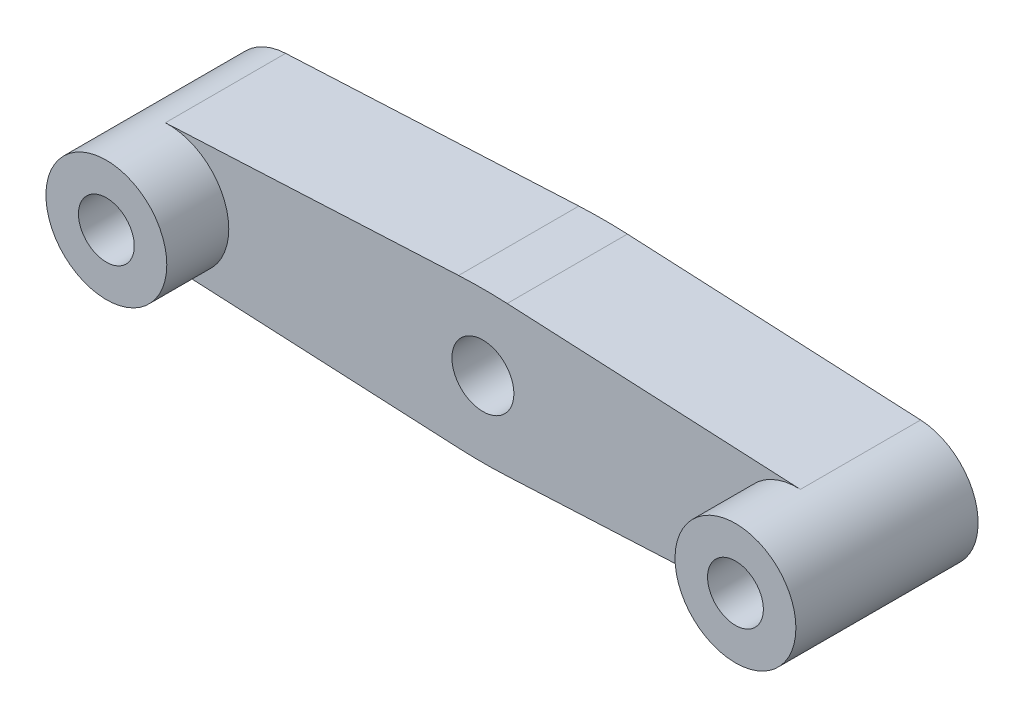
SolidWorks part; units mm, degrees
material "6061 합금"
ref_plane "정면" through (0, 0, 0) normal (0, 0, 1) x (1, 0, 0)
ref_plane "윗면" through (0, 0, 0) normal (0, 1, 0) x (1, 0, 0)
ref_plane "우측면" through (0, 0, 0) normal (1, 0, 0) x (0, 0, -1)
sketch "스케치1" plane through (0, 0, 0) normal (0, 0, 1) x (1, 0, 0)
  line L0 (0, -12.25) -> (0, 12.25) construction
  line L1 (-51.2275, 9.7383) -> (0, 12.25)
  line L2 (-51.2275, -9.7383) -> (0, -12.25)
  line L3 (51.2275, -9.7383) -> (0, -12.25)
  line L4 (51.2275, 9.7383) -> (0, 12.25)
  circle A0 centre (-50.75, 0) radius 9.75
  circle A1 centre (50.75, 0) radius 9.75
  dimension "D1" = 24.5
  dimension "D2" = 19.5
  dimension "D3" = 101.5
extrude "보스-돌출1" add sketch "스케치1" along normal blind 19.4 contours A0 | L2 L0 L1 A0 | L0 L3 A1 L4 | A1 region at (-20.9946, 0, 0) region at (20.9946, 0, 0) region at (-50.75, 0, 0) region at (50.75, 0, 0)
extrude "보스-돌출2" add sketch "스케치1<3>" along normal blind 29.4 contours A0 | A1 region at (-50.75, 0, 0) region at (50.75, 0, 0)
sketch "스케치1<3>" plane through (0, 0, 0) normal (0, 0, 1) x (1, 0, 0) same geometry as "스케치1"
sketch "스케치2" plane through (0, 0, 0) normal (0, 0, 1) x (1, 0, 0)
  circle A0 centre (0, 0) radius 5
  dimension "D1" = 10
extrude "컷-돌출1" cut sketch "스케치2" along normal through all
fillet "필렛1" radius 80 2 edges at (0, -12.25, 9.7) (0, 12.25, 9.7)
hole_wizard "M8 소켓 머리 캡 나사용 카운터보어1" positions "스케치3" profile "스케치4" counterbore size "M8" standard "Ansi Metric" end condition through all
sketch "스케치3" plane through (0, 0, 0) normal (0, 0, -1) x (-1, 0, 0)
  point P0 (-50.75, 0)
  point P3 (50.75, 0)
sketch "스케치4" plane through (50.75, 0, 0) normal (1, 0, 0) x (0, 1, 0)
  line L0 (0, 0) -> (0, 29.4)
  line L1 (0, 29.4) -> (4.5, 29.4)
  line L3 (4.5, 29.4) -> (4.5, 8)
  line L4 (4.5, 8) -> (7.5, 8)
  line L5 (7.5, 8) -> (7.5, 0)
  line L7 (7.5, 0) -> (0, 0)
  line L11 (0, -6.35) -> (0, 107.95) construction
  dimension "관통 구멍 지름" = 9
  dimension "관통 구멍 깊이" = 29.4
  dimension "카운터보어 지름" = 15
  dimension "카운터보어 깊이" = 8
